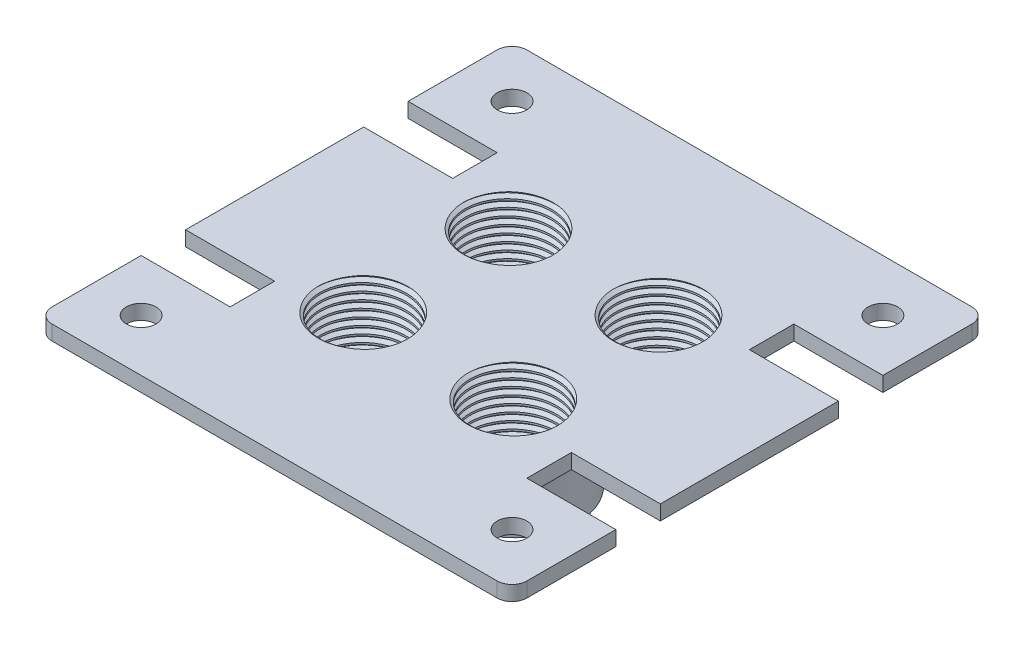
SolidWorks part; units mm, degrees
ref_plane "Front Plane" through (0, 0, 0) normal (0, 0, 1) x (1, 0, 0)
ref_plane "Top Plane" through (0, 0, 0) normal (0, 1, 0) x (1, 0, 0)
ref_plane "Right Plane" through (0, 0, 0) normal (1, 0, 0) x (0, 0, -1)
sketch "Sketch1" plane through (0, 0, 0) normal (0, 1, 0) x (1, 0, 0)
  line L0 (0, 32) -> (0, -32) construction
  line L1 (-32, -32) -> (32, -32)
  line L2 (-32, -32) -> (-32, 32)
  line L3 (-32, 32) -> (32, 32)
  line L4 (32, -32) -> (32, 32)
  line L5 (-32, -32) -> (32, 32) construction
  line L6 (-32, 32) -> (32, -32) construction
  line L7 (-32, 0) -> (32, 0) construction
  line L8 (32, 18) -> (20, 18) construction
  line L9 (32, -12) -> (20, -12) construction
  line L10 (32, -12) -> (32, -18) construction
  line L11 (32, -18) -> (20, -18) construction
  line L12 (20, -12) -> (20, -18) construction
  line L13 (20, 12) -> (20, 18) construction
  line L14 (32, 12) -> (20, 12) construction
  line L15 (32, 12) -> (32, 18) construction
  line L16 (-32, -18) -> (-20, -18) construction
  line L17 (-20, -12) -> (-20, -18) construction
  line L18 (-32, -12) -> (-20, -12) construction
  line L19 (-32, -12) -> (-32, -18) construction
  line L20 (-32, 12) -> (-32, 18) construction
  line L21 (-32, 12) -> (-20, 12) construction
  line L22 (-20, 12) -> (-20, 18) construction
  line L23 (-32, 18) -> (-20, 18) construction
  circle A0 centre (25, 25) radius 2
  circle A1 centre (25, -25) radius 2
  circle A2 centre (-25, -25) radius 2
  circle A3 centre (-25, 25) radius 2
  circle A4 centre (10.11, 9.79) radius 8.5
  circle A5 centre (-10.11, 9.79) radius 8.5
  circle A6 centre (10.11, -9.79) radius 8.5
  circle A7 centre (-10.11, -9.79) radius 8.5
  point P0 (0, 0)
  dimension "D4" = 4
  dimension "D5" = 4
  dimension "D6" = 4
  dimension "D7" = 4
  dimension "D13" = 17
  dimension "D1" = 64
  dimension "D2" = 64
  dimension "D3" = 7
  dimension "D8" = 50
  dimension "D9" = 50
  dimension "D10" = 50
  dimension "D11" = 21.89
  dimension "D12" = 22.21
  dimension "D14" = 14
  dimension "D15" = 6
  dimension "D16" = 12
extrude "Boss-Extrude1" add sketch "Sketch1" along normal blind 2
sketch "Sketch4" plane through (0, 0, 0) normal (0, -1, 0) x (1, 0, 0)
  line L0 (0, 32) -> (0, -32) construction
  line L7 (-32, 0) -> (32, 0) construction
  line L8 (32, 18) -> (20, 18)
  line L9 (32, -12) -> (20, -12)
  line L10 (32, -12) -> (32, -18)
  line L11 (32, -18) -> (20, -18)
  line L12 (20, -12) -> (20, -18)
  line L13 (20, 12) -> (20, 18)
  line L14 (32, 12) -> (20, 12)
  line L15 (32, 12) -> (32, 18)
  line L16 (-32, -18) -> (-20, -18)
  line L17 (-20, -12) -> (-20, -18)
  line L18 (-32, -12) -> (-20, -12)
  line L19 (-32, -12) -> (-32, -18)
  line L20 (-32, 12) -> (-32, 18)
  line L21 (-32, 12) -> (-20, 12)
  line L22 (-20, 12) -> (-20, 18)
  line L23 (-32, 18) -> (-20, 18)
  point P0 (0, 0)
  dimension "D15" = 6
  dimension "D16" = 12
extrude "Cut-Extrude1" cut sketch "Sketch4" against normal blind 3
sketch "Sketch5" plane through (0, 0, 0) normal (0, -1, 0) x (1, 0, 0)
  circle A0 centre (-10.11, 9.79) radius 8.5
  circle A1 centre (10.11, 9.79) radius 8.5
  circle A2 centre (-10.11, -9.79) radius 8.5
  circle A3 centre (10.11, -9.79) radius 8.5
  circle A4 centre (10.11, 9.79) radius 6.367
  circle A6 centre (-10.11, 9.79) radius 6.367
  circle A7 centre (-10.11, -9.79) radius 6.367
  circle A8 centre (10.11, -9.79) radius 6.3678
extrude "Boss-Extrude2" add sketch "Sketch5" along normal blind 10 from surface at -2 starting at face at (0, 2, 0)
thread "Thread2" pitch 1 start angle 0, offset 3, length 22, pitch 1, diameter 12.734
ref_plane "Plane3" through (-16.477, 5, -9.79) normal (0, 0, 1) x (-1, 0, 0)
sketch "Thread Profile3" plane through (-16.477, 5, -9.79) normal (0, 0, 1) x (-1, 0, 0)
  line L0 (0, 0) -> (0, 1) construction
  line L11 (0, 0) -> (0, 0.875)
  line L12 (0, 0.875) -> (-0.5413, 0.5625)
  line L13 (-0.5413, 0.5625) -> (-0.5413, 0.3125)
  line L15 (-0.5413, 0.3125) -> (0, 0)
  line L17 (-0.5413, 0.4375) -> (0, 0.4375) construction
  point P2 (0, 0)
  dimension "Pitch" = 1
  dimension "Profile_Angle" = 60
  dimension "Profile_Land" = 0.25
  dimension "Profile_Height" = 0.5413
thread "Thread3" pitch 1 profile "Thread Profile4" start angle 0, offset 3, length 22, pitch 1, diameter 12.7357
ref_plane "Plane4" through (3.7422, 5, -9.79) normal (0, 0, 1) x (-1, 0, 0)
sketch "Thread Profile4" plane through (3.7422, 5, -9.79) normal (0, 0, 1) x (-1, 0, 0)
  line L0 (0, 0) -> (0, 1) construction
  line L11 (0, 0) -> (0, 0.875)
  line L12 (0, 0.875) -> (-0.5413, 0.5625)
  line L13 (-0.5413, 0.5625) -> (-0.5413, 0.3125)
  line L15 (-0.5413, 0.3125) -> (0, 0)
  line L17 (-0.5413, 0.4375) -> (0, 0.4375) construction
  point P2 (0, 0)
  dimension "Pitch" = 1
  dimension "Profile_Angle" = 60
  dimension "Profile_Land" = 0.25
  dimension "Profile_Height" = 0.5413
thread "Thread4" pitch 1 profile "Thread Profile5" start angle 0, offset 3, length 22, pitch 1, diameter 12.734
ref_plane "Plane5" through (3.743, 5, 9.79) normal (0, 0, 1) x (-1, 0, 0)
sketch "Thread Profile5" plane through (3.743, 5, 9.79) normal (0, 0, 1) x (-1, 0, 0)
  line L0 (0, 0) -> (0, 1) construction
  line L11 (0, 0) -> (0, 0.875)
  line L12 (0, 0.875) -> (-0.5413, 0.5625)
  line L13 (-0.5413, 0.5625) -> (-0.5413, 0.3125)
  line L15 (-0.5413, 0.3125) -> (0, 0)
  line L17 (-0.5413, 0.4375) -> (0, 0.4375) construction
  point P2 (0, 0)
  dimension "Pitch" = 1
  dimension "Profile_Angle" = 60
  dimension "Profile_Land" = 0.25
  dimension "Profile_Height" = 0.5413
thread "Thread5" pitch 1 profile "Thread Profile6" start angle 0, offset 3, length 22, pitch 1, diameter 12.734
ref_plane "Plane6" through (-16.477, 5, 9.79) normal (0, 0, 1) x (-1, 0, 0)
sketch "Thread Profile6" plane through (-16.477, 5, 9.79) normal (0, 0, 1) x (-1, 0, 0)
  line L0 (0, 0) -> (0, 1) construction
  line L11 (0, 0) -> (0, 0.875)
  line L12 (0, 0.875) -> (-0.5413, 0.5625)
  line L13 (-0.5413, 0.5625) -> (-0.5413, 0.3125)
  line L15 (-0.5413, 0.3125) -> (0, 0)
  line L17 (-0.5413, 0.4375) -> (0, 0.4375) construction
  point P2 (0, 0)
  dimension "Pitch" = 1
  dimension "Profile_Angle" = 60
  dimension "Profile_Land" = 0.25
  dimension "Profile_Height" = 0.5413
fillet "Fillet1" radius 2 1 edges at (32, 1, -32)
fillet "Fillet2" radius 2 1 edges at (32, 1, 32)
fillet "Fillet3" radius 2 1 edges at (-32, 1, 32)
fillet "Fillet4" radius 2 1 edges at (-32, 1, -32)
